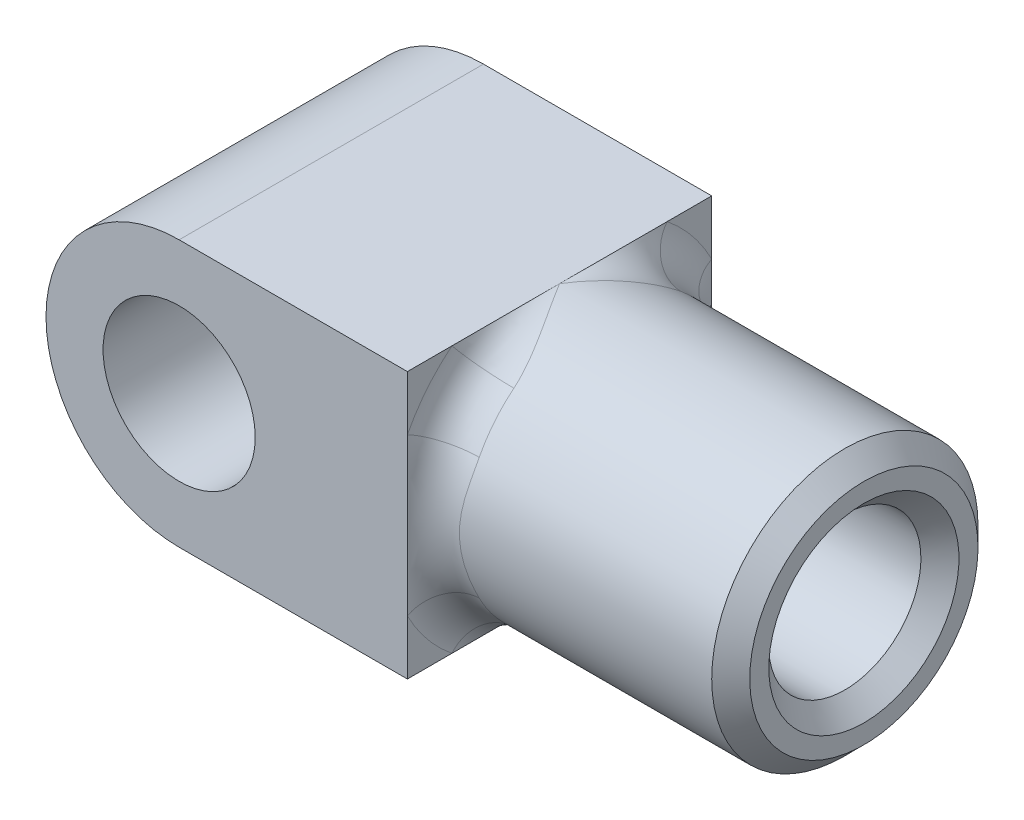
SolidWorks part; units mm, degrees
ref_plane "Front Plane" through (0, 0, 0) normal (0, 0, 1) x (1, 0, 0)
ref_plane "Top Plane" through (0, 0, 0) normal (0, 1, 0) x (1, 0, 0)
ref_plane "Right Plane" through (0, 0, 0) normal (1, 0, 0) x (0, 0, -1)
sketch "Sketch1" plane through (0, 0, 0) normal (0, 0, 1) x (1, 0, 0)
  line L1 (3, -3.5) -> (-3, -3.5)
  line L2 (3, -3.5) -> (3, 3.5)
  line L3 (3, 3.5) -> (-3, 3.5)
  arc A0 (-3, 3.5) -> (-3, -3.5) centre (-3, 0) ccw
  circle A1 centre (-3, 0) radius 2
  dimension "D1" = 7
  dimension "D2" = 4
extrude "Boss-Extrude1" add sketch "Sketch1" along normal mid plane 8
sketch "Sketch2" plane through (3, 0, 0) normal (1, 0, 0) x (0, 0, -1)
  circle A0 centre (0, 0) radius 3.5
  circle A1 centre (0, 0) radius 2
  dimension "D1" = 7
  dimension "D2" = 4
extrude "Boss-Extrude2" add sketch "Sketch2" along normal blind 8
sketch "Sketch3" plane through (3, 0, 0) normal (1, 0, 0) x (0, 0, -1)
  circle A1 centre (0, 0) radius 2
  circle A2 centre (0, 0) radius 2
  dimension "D1" = 0
extrude "Cut-Extrude1" cut sketch "Sketch3" against normal blind 2
chamfer "Chamfer1" distance 0.5 angle 45 2 edges at (11, 2, 0) (11, 3.5, 0)
fillet "Fillet1" radius 1 2 edges at (3, 0, -3.5) (3, 0, 3.5)
